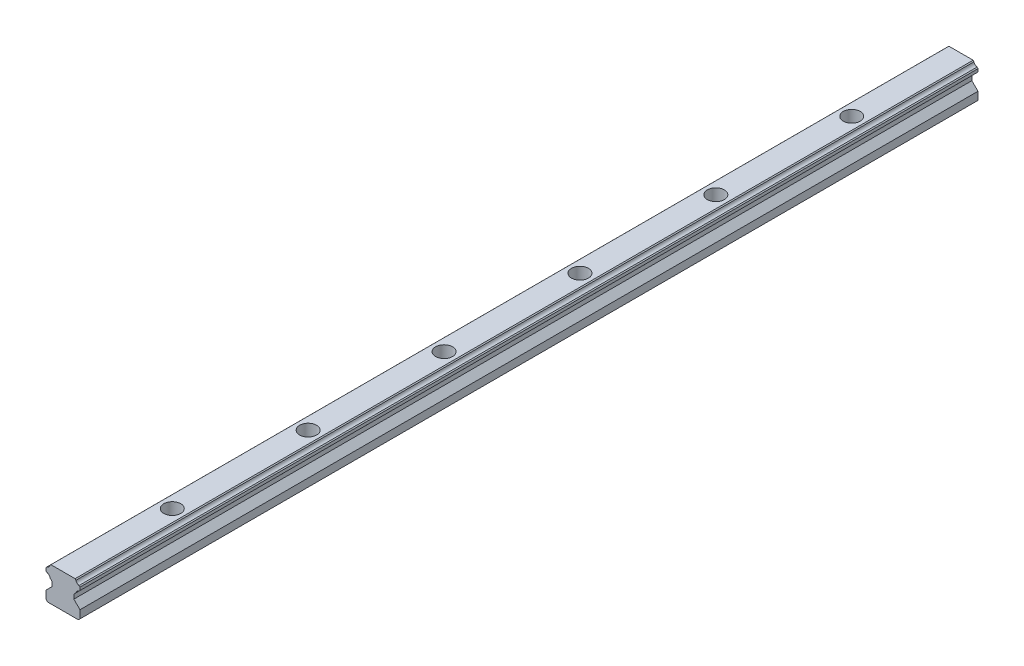
SolidWorks part; units mm, degrees
ref_plane "Front Plane" through (0, 0, 0) normal (0, 0, 1) x (1, 0, 0)
ref_plane "Top Plane" through (0, 0, 0) normal (0, 1, 0) x (1, 0, 0)
ref_plane "Right Plane" through (0, 0, 0) normal (1, 0, 0) x (0, 0, -1)
sketch "Sketch1" plane through (-20, 0, 0) normal (0, 0, 1) x (1, 0, 0)
  line L0 (12.5, 0.7) -> (13.2, 0)
  line L1 (13.2, 0) -> (26.8, 0)
  line L2 (27.5, 4.2) -> (27.5, 0.7)
  line L3 (24.8, 6.9) -> (27.5, 4.2)
  line L4 (24.8, 8.84) -> (24.8, 6.9)
  line L5 (25.7559, 9.7942) -> (24.8, 8.84)
  line L6 (27.5, 11.54) -> (27.0943, 11.1343)
  line L7 (27.5, 12.85) -> (27.5, 11.54)
  line L8 (27.0943, 13.2684) -> (27.5, 12.85)
  line L9 (25.35, 15) -> (25.7559, 14.5941)
  line L10 (27.5, 0.7) -> (26.8, 0)
  line L11 (25.35, 15) -> (14.65, 15)
  line L12 (14.65, 15) -> (14.2441, 14.5941)
  line L13 (12.9057, 13.2684) -> (12.5, 12.85)
  line L14 (12.5, 12.85) -> (12.5, 11.54)
  line L15 (12.5, 11.54) -> (12.9057, 11.1343)
  line L16 (14.2441, 9.7942) -> (15.2, 8.84)
  line L17 (15.2, 8.84) -> (15.2, 6.9)
  line L18 (15.2, 6.9) -> (12.5, 4.2)
  line L19 (12.5, 4.2) -> (12.5, 0.7)
  line L20 (20, 15) -> (20, 0) construction
  arc A0 (27.0943, 11.1343) -> (25.7559, 9.7942) centre (27.3023, 9.5882) ccw
  arc A1 (25.7559, 14.5941) -> (27.0943, 13.2684) centre (27.3003, 14.8148) ccw
  arc A2 (14.2441, 14.5941) -> (12.9057, 13.2684) centre (12.6997, 14.8148) cw
  arc A3 (12.9057, 11.1343) -> (14.2441, 9.7942) centre (12.6977, 9.5882) cw
  dimension "D14" = 1.56
  dimension "D1" = 15
  dimension "D2" = 0.7
  dimension "D3" = 0.7
  dimension "D4" = 4.2
  dimension "D5" = 6.9
  dimension "D6" = 8.84
  dimension "D7" = 4.8
  dimension "D8" = 5.7559
  dimension "D9" = 0.4059
  dimension "D10" = 0.4059
  dimension "D11" = 1.7316
  dimension "D12" = 2.15
  dimension "D13" = 3.46
  dimension "D15" = 7.0943
  dimension "D16" = 3.8657
  dimension "D17" = 5.2058
  dimension "D18" = 15
extrude "Extrude1" add sketch "Sketch1" against normal blind 460
sketch "Sketch2" plane through (0, 0, 0) normal (1, 0, 0) x (0, 0, -1)
  line L0 (20, 15) -> (23.75, 15)
  line L1 (23.75, 15) -> (23.75, 9.7)
  line L2 (23.75, 9.7) -> (22.25, 9.7)
  line L3 (22.25, 9.7) -> (22.25, 0)
  line L4 (22.25, 0) -> (20, 0)
  line L5 (20, 0) -> (20, 15) construction
  line L6 (20, 0) -> (20, 15) construction
  line L7 (20, 15) -> (20, 0)
  line L8 (460, 0) -> (0, 0) construction
  line L9 (460, 15) -> (0, 15) construction
  dimension "D1" = 5.3
  dimension "D2" = 7.5
  dimension "D3" = 4.5
  dimension "D4" = 20
revolve "Cut-Revolve1" cut sketch "Sketch2" angle 360 about L6 reverse direction yes
ref_axis "Axis1" through (0, 0, -168) along (0, 0, 1)
pattern_linear "LPattern1" count 8 spacing 60 along (0, 0, -1) of "Cut-Revolve1"
sketch "Sketch3" plane through (0, 0, 0) normal (0, -1, 0) x (1, 0, 0)
  line L0 (-6.8, 0) -> (6.8, 0) construction
  line L1 (14.5013, 0) -> (-20.8708, 0)
  line L2 (14.5013, 0) -> (14.5013, -31.75)
  line L3 (14.5013, -31.75) -> (-20.8708, -31.75)
  line L4 (-20.8708, 0) -> (-20.8708, -31.75)
  line L16 (-9.5504, -428.244) -> (-17.1637, -428.244)
  line L17 (-17.1637, -428.244) -> (-17.1637, -476.0075)
  line L18 (-17.1637, -476.0075) -> (14.5013, -476.0075)
  line L19 (14.5013, -476.0075) -> (14.5013, -428.244)
  line L20 (14.5013, -428.244) -> (-17.1637, -428.244)
  circle M7 centre (0, -20) radius 2.25
  line M8 (6.8, 0) -> (-6.8, 0)
  line M9 (-6.8, 0) -> (-6.8, -460)
  line M10 (-6.8, -460) -> (6.8, -460)
  line M11 (6.8, -460) -> (6.8, 0)
  circle M15 centre (0, -440) radius 2.25
extrude "Cut-Extrude1" cut sketch "Sketch3" against normal through all contours L19 L20 L16 L17 L18 M11 M10 M9 | L1 L4 L3 M9 | L3 L2 L1 M11 | L3 M11 M8 M9 M7 | L20 M11 M9 M10 M15 region at (10.6507, 0, -15.875) region at (0, 0, -15.7173) region at (-13.8354, 0, -15.875) region at (0, 0, -444.2796) region at (10.6507, 0, -428.8171)
